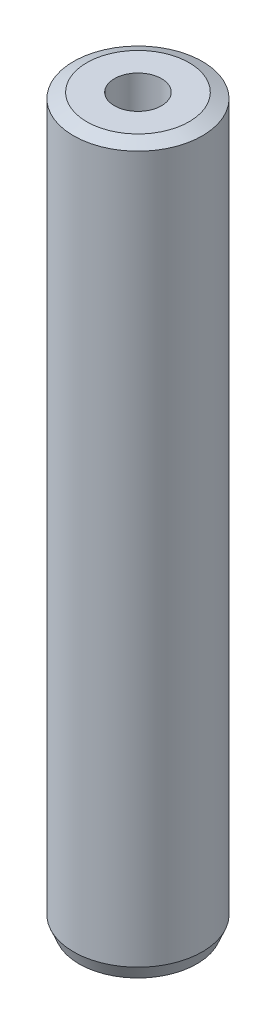
SolidWorks part; units mm, degrees
ref_plane "Front Plane" through (0, 0, 0) normal (0, 0, 1) x (1, 0, 0)
ref_plane "Top Plane" through (0, 0, 0) normal (0, 1, 0) x (1, 0, 0)
ref_plane "Right Plane" through (0, 0, 0) normal (1, 0, 0) x (0, 0, -1)
sketch "Sketch1" plane through (0, 0, 0) normal (0, 1, 0) x (1, 0, 0)
  circle A0 centre (0, 0) radius 47.5
  dimension "SHAFT_OD" = 95
extrude "Boss-Extrude1" add sketch "Sketch1" along normal blind 534.7693
sketch "Sketch2" plane through (0, 0, 0) normal (0, 1, 0) x (1, 0, 0)
  circle A0 centre (0, 0) radius 17.3536
  dimension "BORE_D" = 34.7073
extrude "Cut-Extrude1" cut sketch "Sketch2" along normal through all
chamfer "Chamfer1" distance 4.0888 angle 67.299 2 edges at (0, 534.7693, 47.5) (0, 0, 47.5) first distance on face at (0, 534.7693, 47.5) first distance on face at (0, 0, 17.3536)
